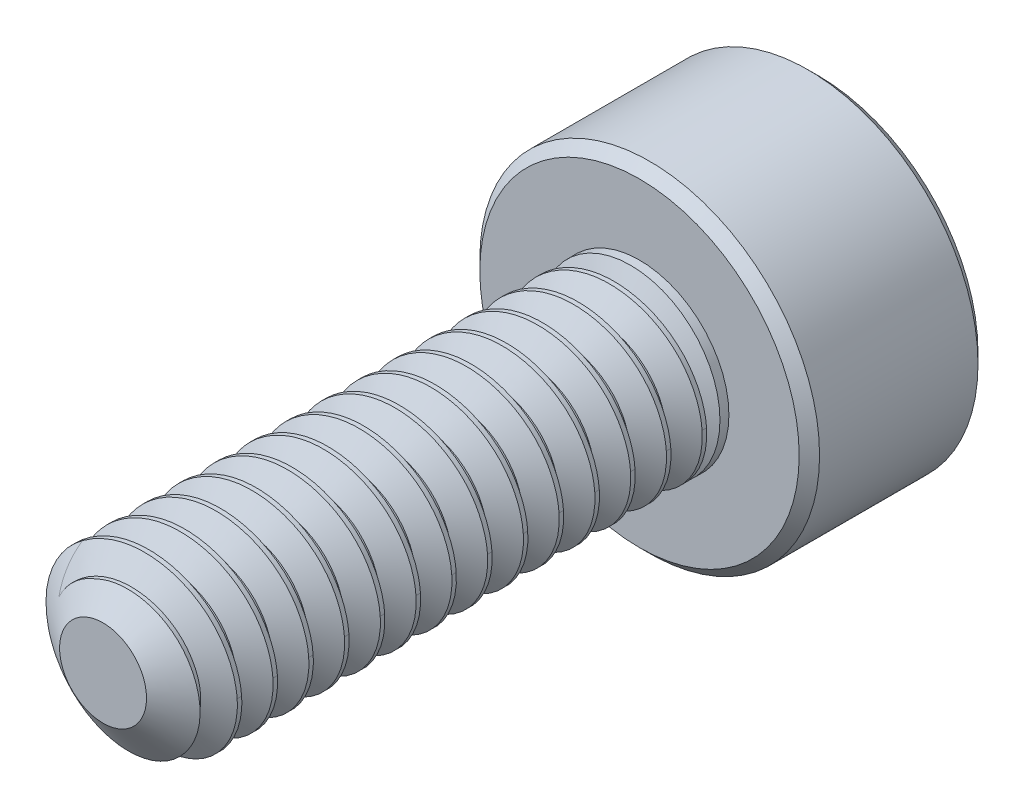
SolidWorks part; units mm, degrees
ref_plane "Front Plane" through (0, 0, 0) normal (0, 0, 1) x (1, 0, 0)
ref_plane "Top Plane" through (0, 0, 0) normal (0, 1, 0) x (1, 0, 0)
ref_plane "Right Plane" through (0, 0, 0) normal (1, 0, 0) x (0, 0, -1)
sketch "Sketch1" plane through (0, 0, 0) normal (0, 0, 1) x (1, 0, 0)
  circle A0 centre (0, 0) radius 1
  dimension "OD" = 2
extrude "Extrude1" add sketch "Sketch1" against normal blind 6
sketch "Sketch2" plane through (0, 0, 0) normal (0, 0, 1) x (1, 0, 0)
  circle A0 centre (0, 0) radius 1 construction
  circle A1 centre (0, 0) radius 1
curve "Helix/Spiral1" pitch 0.4 height 6.4 radius 1 centre (0, 0, 0) axis (0, 0, -1) start towards (0, 1, 0) parameters "pitch"=0.4
sketch "Sketch3" plane through (0, 0, 0) normal (1, 0, 0) x (0, 0, -1)
  line L0 (-0.35, 1) -> (-0.2, 0.7402)
  line L1 (-0.2, 0.7402) -> (-0.15, 0.7402)
  line L2 (-0.15, 0.7402) -> (0, 1)
  line L3 (-0.35, 1) -> (0, 1)
  line L4 (-0.175, 1) -> (-0.175, 0.7402) construction
  line L5 (-0.275, 0.8701) -> (-0.075, 0.8701) construction
  line L6 (0, 1) -> (0, -1) construction
  line L7 (0, -1) -> (6, -1) construction
  point P11 (1.8, -1)
  dimension "D1" = 0.05
  dimension "D2" = 0.2
  dimension "D3" = 60
  dimension "D4" = 1.8
sweep "Cut-Sweep1" cut profiles "Sketch3" path "Helix/Spiral1" align with end faces yes
sketch "Sketch4" plane through (0, 0, 0) normal (1, 0, 0) x (0, 0, -1)
  line L0 (0.3598, 1) -> (0, 0.4862)
  line L1 (0, 0.4862) -> (0, 1)
  line L2 (0.3598, 1) -> (0, 1)
  line L3 (-0.35, 1) -> (0, 1) construction
  line L4 (0, 0) -> (7.0209, 0) construction
  dimension "D1" = 55
  dimension "D2" = 0.254
revolve "Cut-Revolve1" cut sketch "Sketch4" angle 360 about L4
sketch "Sketch5" plane through (0, 0, 0) normal (1, 0, 0) x (0, 0, -1)
  line L0 (6, -0.7473) -> (6, 0.7135) construction
  line L1 (6, 1) -> (0.1203, 1)
  line L2 (6, 1) -> (6, 0)
  line L3 (6, 0) -> (0.0001, 0)
  line L4 (0.0001, 0.6698) -> (0.0001, 0)
  line L5 (0.1203, 1) -> (0.0001, 0.6698)
  line L6 (0, 0) -> (9.9695, 0) construction
  point P3 (0.0001, 1)
  point P10 (0.0001, 1)
  dimension "D1" = 0.3302
  dimension "Thread min" = 0.0001
  dimension "D3" = 20
revolve "partially thread" [suppressed] add sketch "Sketch5" angle 360 about L6
sketch "Sketch6" plane through (0, 0, -6) normal (0, 0, -1) x (-1, 0, 0)
  circle A0 centre (0, 0) radius 1.9
  dimension "head dia" = 3.8
extrude "Extrude2" add sketch "Sketch6" along normal blind 2
sketch "Sketch7" plane through (0, 0, -8) normal (0, 0, -1) x (-1, 0, 0)
  line L1 (0, 0.866) -> (-0.75, 0.433)
  line L2 (-0.75, 0.433) -> (-0.75, -0.433)
  line L3 (-0.75, -0.433) -> (0, -0.866)
  line L4 (0, -0.866) -> (0.75, -0.433)
  line L5 (0.75, -0.433) -> (0.75, 0.433)
  line L6 (0.75, 0.433) -> (0, 0.866)
  circle A0 centre (0, 0) radius 0.75 construction
  dimension "hex dia" = 1.5
extrude "Cut-Extrude1" cut sketch "Sketch7" against normal blind 1.125
sketch "Sketch8" plane through (0, 0, -8) normal (0, 0, -1) x (-1, 0, 0)
  circle A0 centre (0, 0) radius 0.866
extrude "Cut-Extrude2" cut sketch "Sketch8" against normal through all draft 45
chamfer "Chamfer1" distance 0.114 angle 45 2 edges at (-1.9, 0, -8) (-1.9, 0, -6)
sketch "Sketch9" plane through (0, 0, 0) normal (1, 0, 0) x (0, 0, -1)
  line L0 (0, 1) -> (0, -1) construction
  line L1 (2.2, 1) -> (2.2, -1) construction
  dimension "D1" = 2.2
sketch "Sketch10" plane through (0, 0, 0) normal (1, 0, 0) x (0, 0, -1)
  line L0 (6, 1) -> (6, 0)
  line L1 (6, 1) -> (5.9, 1)
  line L2 (5.9, 1) -> (5.4858, 0)
  line L3 (6, 0) -> (5.4858, 0)
  line L4 (6, 1.786) -> (6, -1.786) construction
  dimension "D1" = 22.5
  dimension "D2" = 0.1
revolve "Revolve1" add sketch "Sketch10" angle 360 about L3
equation "\"D3@Helix/Spiral1\" = \"screw length@Extrude1\"+\"pitch@Helix/Spiral1\""
equation "\"D1@Sketch3\" = \"pitch@Helix/Spiral1\"*.125"
equation "\"D2@Sketch3\" = \"pitch@Helix/Spiral1\"*.5"
equation "\"D1@Cut-Extrude1\" = \"hex dia@Sketch7\"*.75"
equation "\"D1@Chamfer1\" = \"head dia@Sketch6\"*.03"
equation "\"D1@Sketch9\" = \"pitch@Helix/Spiral1\"*5.5"
equation "\"D2@Sketch10\" = \"pitch@Helix/Spiral1\"*.25"
equation "\"D4@Sketch3\" = \"pitch@Helix/Spiral1\"*4.50"
